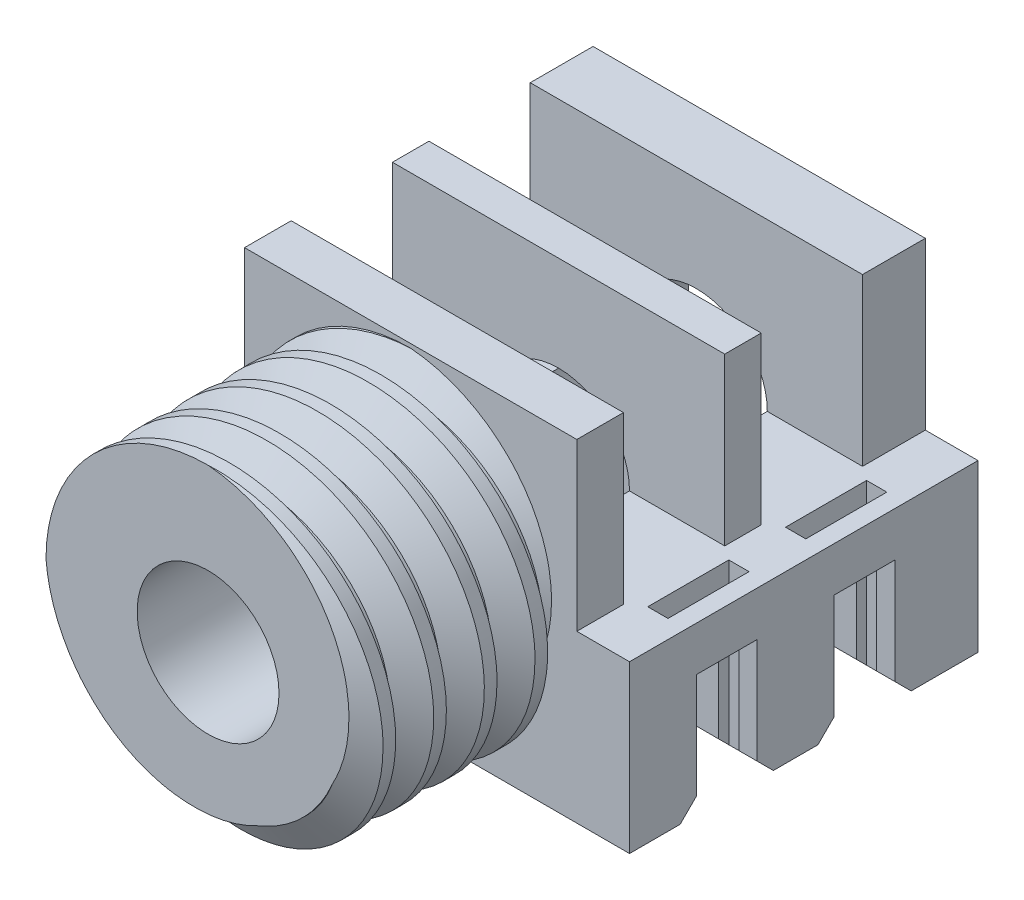
SolidWorks part; units mm, degrees
ref_plane "Front Plane" through (0, 0, 0) normal (0, 0, 1) x (1, 0, 0)
ref_plane "Top Plane" through (0, 0, 0) normal (0, 1, 0) x (1, 0, 0)
ref_plane "Right Plane" through (0, 0, 0) normal (1, 0, 0) x (0, 0, -1)
sketch "Sketch1" plane through (0, 0, 0) normal (0, 0, 1) x (1, 0, 0)
  circle A1 centre (0, 0) radius 4
  dimension "D2" = 8
extrude "Boss-Extrude1" add sketch "Sketch1" along normal blind 5
sketch "Sketch2" plane through (0, 0, 0) normal (0, 0, -1) x (-1, 0, 0)
  line L0 (-4.1, 4.1) -> (4.1, 4.1)
  line L1 (4.1, 4.1) -> (4.1, 0)
  line L2 (4.1, 0) -> (5.4, 0)
  line L3 (5.4, 0) -> (5.4, -4.1)
  line L4 (5.4, -4.1) -> (-5.4, -4.1)
  line L5 (0, 4.1) -> (0, -4.1) construction
  line L6 (-5.4, 0) -> (-5.4, -4.1)
  line L7 (-4.1, 0) -> (-5.4, 0)
  line L8 (-4.1, 4.1) -> (-4.1, 0)
  dimension "D1" = 4.1
  dimension "D2" = 5.4
  dimension "D3" = 8.2
  dimension "D4" = 4.1
extrude "Boss-Extrude2" add sketch "Sketch2" along normal blind 8.6
sketch "Sketch3" plane through (-5.4, 0, 0) normal (-1, 0, 0) x (0, 0, 1)
  line L0 (-1.15, 4.1) -> (-1.15, 0)
  line L1 (-1.15, 0) -> (-3.65, 0)
  line L2 (-3.65, 0) -> (-3.65, 4.1)
  line L3 (-3.65, 4.1) -> (-1.15, 4.1)
  line L4 (-4.55, 4.1) -> (-7.05, 4.1)
  line L5 (-7.05, 4.1) -> (-7.05, 0)
  line L6 (-7.05, 0) -> (-4.55, 0)
  line L7 (-4.55, 0) -> (-4.55, 4.1)
  line L8 (-5.8, -1.1) -> (-6.55, -1.1)
  line L9 (-6.55, -1.1) -> (-6.55, -4.1)
  line L10 (-6.55, -4.1) -> (-5.8, -4.1)
  line L11 (-5.8, -4.1) -> (-5.05, -4.1)
  line L12 (-5.05, -4.1) -> (-5.05, -1.1)
  line L13 (-5.05, -1.1) -> (-5.8, -1.1)
  line L14 (-2.4, -4.1) -> (-1.65, -4.1)
  line L15 (-3.15, -4.1) -> (-2.4, -4.1)
  line L16 (-1.65, -4.1) -> (-1.65, -1.1)
  line L17 (-1.65, -1.1) -> (-2.4, -1.1)
  line L18 (-2.4, -1.1) -> (-3.15, -1.1)
  line L19 (-3.15, -1.1) -> (-3.15, -4.1)
  line L20 (-2.4, 4.1) -> (-2.4, -4.1) construction
  line L21 (-5.8, 4.1) -> (-5.8, -4.1) construction
  line L22 (0, 0) -> (-9.6573, 0) construction
  dimension "D1" = 2.4
  dimension "D2" = 3.4
  dimension "D3" = 4.1
  dimension "D4" = 2.5
  dimension "D5" = 2.5
  dimension "D6" = 1.5
  dimension "D7" = 1.5
  dimension "D8" = 4.1
  dimension "D9" = 3
extrude "Cut-Extrude1" cut sketch "Sketch3" against normal through all and the other way through all
sketch "Sketch4" plane through (0, -4.1, 0) normal (0, -1, 0) x (1, 0, 0)
  line L0 (4.45, -1.4) -> (4.95, -1.4)
  line L1 (-4.95, -1.4) -> (-4.45, -1.4)
  line L2 (-4.95, -1.4) -> (-4.95, -3.4)
  line L3 (-4.95, -3.4) -> (-4.45, -3.4)
  line L4 (-4.45, -1.4) -> (-4.45, -3.4)
  line L5 (-4.95, -1.4) -> (-4.45, -3.4) construction
  line L6 (-4.95, -3.4) -> (-4.45, -1.4) construction
  line L7 (4.45, -1.4) -> (4.45, -3.4)
  line L8 (4.45, -3.4) -> (4.95, -3.4)
  line L9 (4.95, -1.4) -> (4.95, -3.4)
  line L10 (4.45, -1.4) -> (4.95, -3.4) construction
  line L11 (4.45, -3.4) -> (4.95, -1.4) construction
  line L12 (4.45, -4.8) -> (4.95, -4.8)
  line L13 (4.45, -4.8) -> (4.45, -6.8)
  line L14 (4.45, -6.8) -> (4.95, -6.8)
  line L15 (4.95, -4.8) -> (4.95, -6.8)
  line L16 (4.45, -4.8) -> (4.95, -6.8) construction
  line L17 (4.45, -6.8) -> (4.95, -4.8) construction
  line L18 (-4.95, -4.8) -> (-4.45, -4.8)
  line L19 (-4.95, -4.8) -> (-4.95, -6.8)
  line L20 (-4.95, -6.8) -> (-4.45, -6.8)
  line L21 (-4.45, -4.8) -> (-4.45, -6.8)
  line L22 (-4.95, -4.8) -> (-4.45, -6.8) construction
  line L23 (-4.95, -6.8) -> (-4.45, -4.8) construction
  line L24 (-5.4, -5.8) -> (5.4, -5.8) construction
  line L25 (-5.4, -6.55) -> (-5.4, -5.05) construction
  line L26 (5.4, -5.05) -> (5.4, -6.55) construction
  line L27 (-4.7, -8.6) -> (-4.7, 0) construction
  line L28 (5.4, -8.6) -> (-5.4, -8.6) construction
  line L29 (5.4, 0) -> (-5.4, 0) construction
  line L30 (-5.4, -2.4) -> (5.4, -2.4) construction
  line L31 (-5.4, -3.15) -> (-5.4, -1.65) construction
  line L32 (5.4, -1.65) -> (5.4, -3.15) construction
  line L33 (4.7, -8.6) -> (4.7, 0) construction
  point P0 (-4.7, -2.4)
  point P7 (4.7, -2.4)
  point P13 (4.7, -5.8)
  point P18 (-4.7, -5.8)
  point P41 (0, 0)
  point P42 (0, 0)
  point P43 (0, 0)
  point P44 (0, 0)
  point P45 (0, 0)
  dimension "D1" = 4.7
  dimension "D2" = 9.4
  dimension "D3" = 2
  dimension "D4" = 0.5
  dimension "D5" = 2
  dimension "D6" = 2
extrude "Cut-Extrude2" cut sketch "Sketch4" against normal blind 8.6
sketch "Sketch5" plane through (0, 0, 5) normal (0, 0, 1) x (1, 0, 0)
  circle A0 centre (0, 0) radius 1.75
  dimension "D1" = 3.5
extrude "Cut-Extrude3" cut sketch "Sketch5" against normal through all
thread "Thread1" pitch 1.25 method cut trim with end face yes profile "Thread Profile1" start angle 0, offset 1.25, length 6.5, pitch 1.25, diameter 8
ref_plane "Plane4" through (-4, 0, 6.25) normal (0, 1, 0) x (1, 0, 0)
sketch "Thread Profile1" plane through (-4, 0, 6.25) normal (0, 1, 0) x (1, 0, 0)
  line L0 (0, 0) -> (0, 1.25) construction
  line L1 (0, 0) -> (0.6766, 0.3906)
  line L2 (0.6766, 0.3906) -> (0.6766, 0.5469)
  line L3 (0.6766, 0.5469) -> (0, 0.9375)
  line L4 (0.6766, 0.4687) -> (0, 0.4687) construction
  line L11 (0, 0) -> (0, 0.9375)
  point P2 (0, 0)
  dimension "Pitch" = 1.25
  dimension "Profile_Angle" = 60
  dimension "Profile_Land" = 0.1562
  dimension "Profile_Height" = 0.6766
sketch "Sketch10" plane through (-5.4, 0, 0) normal (-1, 0, 0) x (0, 0, 1)
  line L0 (-6.55, -4.1) -> (-6.55, -3.7)
  line L1 (-6.55, -4.1) -> (-6.55, -1.1) construction
  line L2 (-6.55, -3.7) -> (-6.95, -4.1)
  line L3 (-8.6, -4.1) -> (-6.55, -4.1) construction
  line L4 (-6.95, -4.1) -> (-6.55, -4.1)
  line L5 (-5.05, -4.1) -> (-5.05, -3.7)
  line L6 (-5.05, -1.1) -> (-5.05, -4.1) construction
  line L7 (-5.05, -3.7) -> (-4.65, -4.1)
  line L8 (-5.05, -4.1) -> (-3.15, -4.1) construction
  line L9 (-4.65, -4.1) -> (-5.05, -4.1)
  line L10 (-3.15, -4.1) -> (-3.55, -4.1)
  line L11 (-3.55, -4.1) -> (-3.15, -3.7)
  line L12 (-3.15, -4.1) -> (-3.15, -1.1) construction
  line L13 (-3.15, -3.7) -> (-3.15, -4.1)
  line L14 (-1.65, -4.1) -> (-1.65, -3.7)
  line L15 (-1.65, -1.1) -> (-1.65, -4.1) construction
  line L16 (-1.65, -3.7) -> (-1.25, -4.1)
  line L17 (-1.65, -4.1) -> (0, -4.1) construction
  line L18 (-1.25, -4.1) -> (-1.65, -4.1)
  dimension "D1" = 0.4
extrude "Cut-Extrude4" cut sketch "Sketch10" against normal through all
